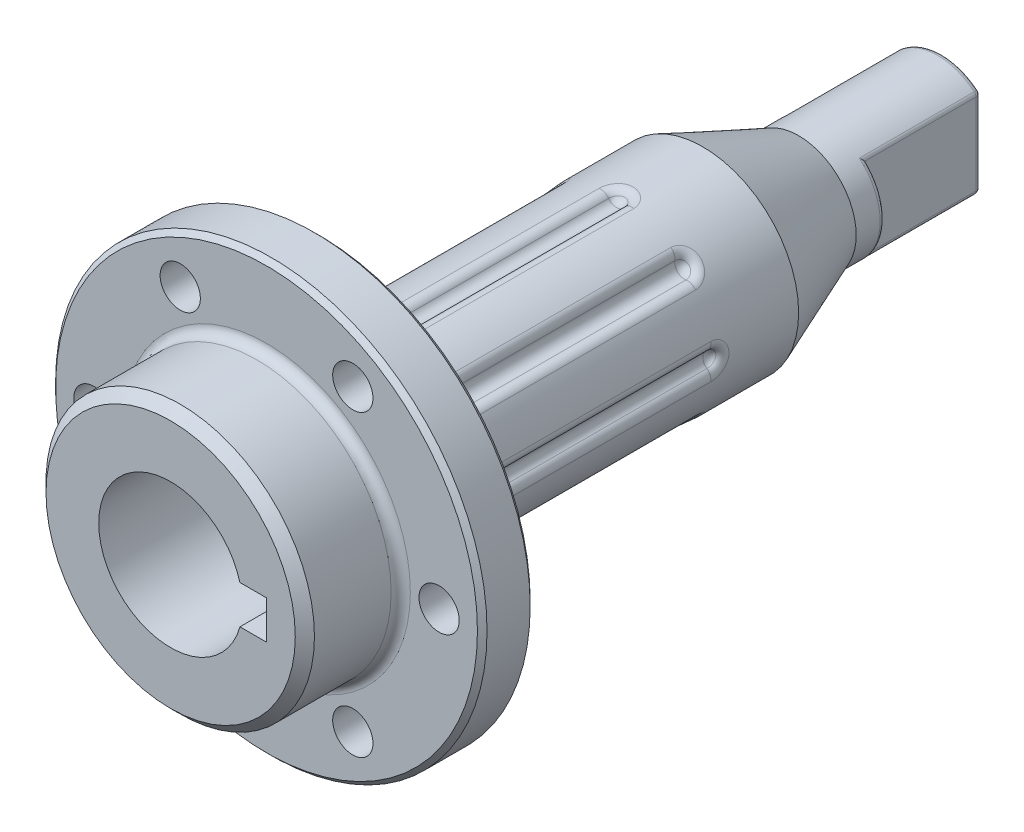
SolidWorks part; units mm, degrees
material "AISI 1010 Steel, hot rolled bar"
ref_plane "Front Plane" through (0, 0, 0) normal (0, 0, 1) x (1, 0, 0)
ref_plane "Top Plane" through (0, 0, 0) normal (0, 1, 0) x (1, 0, 0)
ref_plane "Right Plane" through (0, 0, 0) normal (1, 0, 0) x (0, 0, -1)
sketch "Sketch1" plane through (0, 0, 0) normal (0, 0, 1) x (1, 0, 0)
  circle A0 centre (0, 0) radius 22.5
  dimension "D1" = 45
extrude "Boss-Extrude1" add sketch "Sketch1" along normal mid plane 5.5
sketch "Sketch2" plane through (0, 0, 2.75) normal (0, 0, 1) x (1, 0, 0)
  circle A0 centre (0, 0) radius 14
  dimension "D1" = 28
extrude "Boss-Extrude2" add sketch "Sketch2" along normal blind 10
sketch "Sketch3" plane through (0, 0, 12.75) normal (0, 0, 1) x (1, 0, 0)
  line L0 (0, 0) -> (10, 0) construction
  line L1 (7.2284, -2) -> (10, -2)
  line L3 (7.2284, 2) -> (10, 2)
  line L4 (10, -2) -> (10, 2)
  arc A0 (7.2284, 2) -> (7.2284, -2) centre (0, 0) ccw
  dimension "D1" = 15
  dimension "D2" = 4
  dimension "D3" = 17.5
extrude "Cut-Extrude1" cut sketch "Sketch3" against normal blind 13
sketch "Sketch4" plane through (0, 0, 0) normal (1, 0, 0) x (0, 0, -1)
  line L0 (0, 0) -> (105.3519, 0) construction
  line L1 (2.75, 10) -> (42.75, 10)
  line L2 (2.75, -22.5) -> (2.75, 22.5) construction
  line L3 (42.75, 10) -> (52.75, 6)
  line L4 (52.75, 6) -> (67.75, 6)
  line L5 (67.75, 6) -> (67.75, 0)
  line L6 (-12.75, 14) -> (-12.75, -14) construction
  line L7 (67.75, 0) -> (2.75, 0)
  line L8 (2.75, 10) -> (2.75, 0)
  dimension "D1" = 20
  dimension "D2" = 12
  dimension "D3" = 15
  dimension "D4" = 80.5
  dimension "D5" = 10
revolve "Revolve1" add sketch "Sketch4" angle 360 about L0
sketch "Sketch5" plane through (0, 0, -67.75) normal (0, 0, -1) x (-1, 0, 0)
  line L2 (4, -4.4721) -> (4, 4.4721)
  line L4 (-4, -4.4721) -> (-4, 4.4721)
  line L5 (0, 0) -> (0, 6) construction
  circle A4 centre (0, 0) radius 6 construction
  arc A5 (-4, 4.4721) -> (-4, -4.4721) centre (0, 0) ccw
  arc A6 (4, -4.4721) -> (4, 4.4721) centre (0, 0) ccw
  point P0 (0, 0)
  dimension "D1" = 8
extrude "Cut-Extrude2" cut sketch "Sketch5" against normal blind 12
sketch "Sketch6" plane through (0, 0, 0) normal (1, 0, 0) x (0, 0, -1)
  line L0 (33.75, 10) -> (8.75, 10) construction
  line L1 (42.75, 10) -> (2.75, 10) construction
  line L3 (33.75, 11) -> (8.75, 11)
  line L4 (2.75, -22.5) -> (2.75, 22.5) construction
  line L6 (34.75, 10) -> (7.75, 10)
  arc A0 (34.75, 10) -> (33.75, 11) centre (33.75, 10) ccw
  arc A1 (8.75, 11) -> (7.75, 10) centre (8.75, 10) ccw
  dimension "D1" = 1
  dimension "D2" = 25
  dimension "D3" = 6
  dimension "D4" = 1
revolve "Cut-Revolve4" cut sketch "Sketch6" angle 360 about L0
fillet "Fillet1" radius 1 4 edges at (0.1137, 9.9994, -34.7435) (-0.9987, 9.95, -21.25) (-0.1137, 9.9994, -7.7565) (0.9987, 9.95, -21.25)
pattern_circular "CirPattern1" count 8 over 360 about axis through (0, 0, 0) along (0, 0, 1) of "Cut-Revolve4", "Fillet1" reverse direction yes
hole_wizard "M5x0.8 Tapped Hole1" positions "Sketch7" profile "Sketch8" tap size "M5x0.8" standard "ANSI Metric"
sketch "Sketch7" plane through (0, 0, 2.75) normal (0, 0, 1) x (1, 0, 0)
  circle A0 centre (0, 0) radius 18 construction
  point P4 (-18, 0)
  point P10 (-9, 15.5885)
  point P11 (9, 15.5885)
  point P12 (18, 0)
  point P13 (9, -15.5885)
  point P14 (-9, -15.5885)
  dimension "D1" = 36
  dimension "D2" = 6
sketch "Sketch8" plane through (-9, -15.5885, 2.75) normal (1, 0, 0) x (0, -1, 0)
  line L0 (0, 0) -> (0, 15.2618)
  line L1 (0, 15.2618) -> (2.1, 14)
  line L2 (2.1, 14) -> (2.1, 0)
  line L5 (2.1, 0) -> (0, 0)
  line L10 (0, 15.2618) -> (-2.1, 14) construction
  line L11 (0, -6.35) -> (0, 107.95) construction
  dimension "Tap Drill Dia." = 4.2
  dimension "Tap Drill Depth" = 14
  dimension "Drill Angle" = 118
cosmetic thread "Hole Thread2" parameters "D1"=10, "D2"=5
cosmetic thread "Hole Thread3" parameters "D1"=10, "D2"=5
cosmetic thread "Hole Thread4" parameters "D1"=10, "D2"=5
cosmetic thread "Hole Thread5" parameters "D1"=10, "D2"=5
cosmetic thread "Hole Thread6" parameters "D1"=10, "D2"=5
cosmetic thread "Hole Thread7" parameters "D1"=10, "D2"=5
fillet "Fillet2" radius 1 2 edges at (14, 0, 2.75) (10, 0, -2.75)
chamfer "Chamfer1" distance 1 angle 45 1 edges at (14, 0, 12.75)
chamfer "Chamfer2" distance 0.5 angle 45 2 edges at (22.5, 0, -2.75) (22.5, 0, 2.75)
fillet "Fillet3" radius 0.5 10 edges at (4, 4.4721, -61.75) (-4, 4.4721, -61.75) (0, 6, -67.75) (0, -6, -67.75) (-4, -4.4721, -61.75) (-4, 0, -67.75) (4, 0, -67.75) (4, -4.4721, -61.75) (6, 0, -55.75) (-6, 0, -55.75)
sketch "Sketch11" plane through (0, 0, 0) normal (1, 0, 0) x (0, 0, -1)
  line L0 (67.75, 0) -> (65.75, 0) construction
  line L2 (65.75, 0) -> (67.75, 2)
  line L3 (67.75, 2) -> (67.75, 0)
  line L4 (67.75, 0) -> (65.75, 0)
  line L5 (67.75, -4.4721) -> (67.75, 4.4721) construction
  dimension "D1" = 45
  dimension "D2" = 2
revolve "Cut-Revolve5" cut sketch "Sketch11" angle 360 about L0 region at (0, 0.6667, -67.0833)
